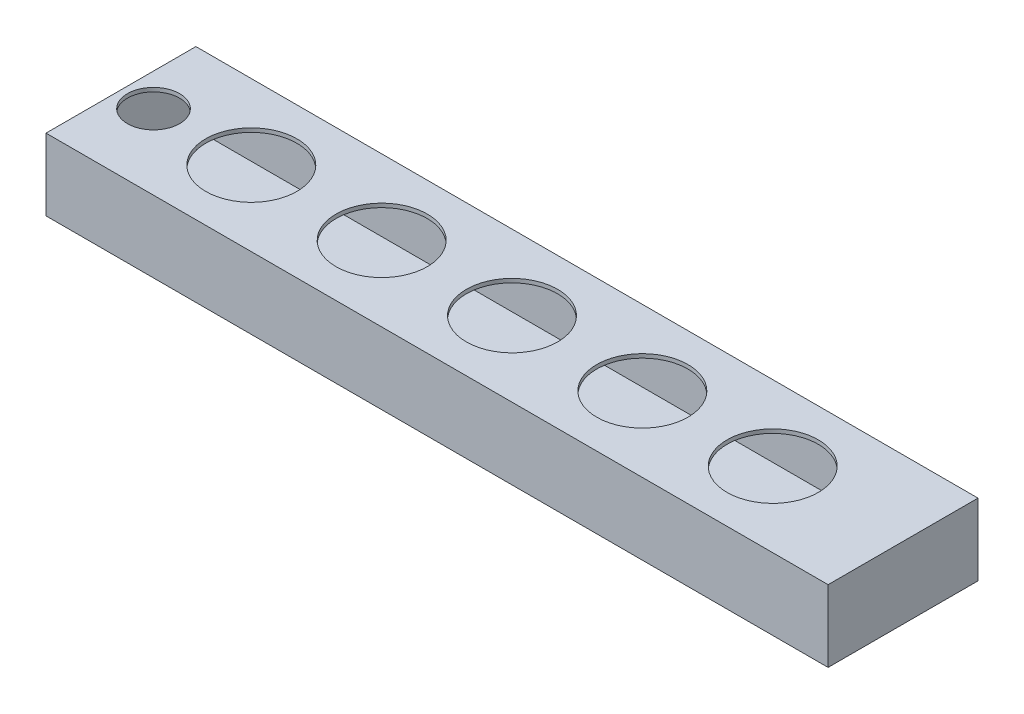
SolidWorks part; units mm, degrees
ref_plane "Спереди" through (0, 0, 0) normal (0, 0, 1) x (1, 0, 0)
ref_plane "Сверху" through (0, 0, 0) normal (0, 1, 0) x (1, 0, 0)
ref_plane "Справа" through (0, 0, 0) normal (1, 0, 0) x (0, 0, -1)
sketch "Эскиз2" plane through (0, 0, 0) normal (0, 0, 1) x (1, 0, 0)
  line L0 (0, 0) -> (600, 0)
  line L1 (600, 0) -> (600, 55)
  line L2 (600, 55) -> (0, 55)
  line L3 (0, 55) -> (0, 0)
extrude "Бобышка-Вытянуть1" add sketch "Эскиз2" along normal blind 115
sketch "Эскиз3" plane through (600, 0, 0) normal (1, 0, 0) x (0, 0, -1)
  line L3 (-112, 52) -> (-3, 52)
  line L4 (-3, 52) -> (-3, 3)
  line L5 (-3, 3) -> (-112, 3)
  line L6 (-112, 3) -> (-112, 52)
  line L7 (-115, 55) -> (-112, 52)
  line L8 (-3, 3) -> (0, 0)
  line L9 (-115, 0) -> (-115, 55) construction
  dimension "D1" = 3
  dimension "D2" = 3
extrude "Вырез-Вытянуть1" cut sketch "Эскиз3" against normal blind 600 contours L6 L5 L4 L3 region at (600, 27.5, 57.5)
sketch "Эскиз4" plane through (0, 55, 0) normal (0, 1, 0) x (1, 0, 0)
  line L0 (600, 0) -> (0, 0) construction
  line L1 (600, -115) -> (597, -115)
  line L2 (600, -115) -> (600, 0)
  line L3 (600, 0) -> (597, 0)
  line L4 (597, -115) -> (597, 0)
  line L6 (0, -115) -> (3, -115)
  line L7 (0, -115) -> (0, 0)
  line L8 (0, 0) -> (3, 0)
  line L9 (3, -115) -> (3, 0)
extrude "Бобышка-Вытянуть2" add sketch "Эскиз4" against normal blind 55
sketch "Эскиз5" plane through (0, 55, 0) normal (0, 1, 0) x (1, 0, 0)
  line L0 (0, -115) -> (5, -115)
  line L1 (600, -115) -> (0, -115) construction
  line L2 (5, -115) -> (5, -57.5)
  line L4 (0, -115) -> (0, 0) construction
  circle A0 centre (25, -57.5) radius 20
  circle A1 centre (100, -57.5) radius 35
  circle A2 centre (200, -57.5) radius 35
  circle A3 centre (300, -57.5) radius 35
  circle A4 centre (400, -57.5) radius 35
  circle A5 centre (500, -57.5) radius 35
  dimension "D3" = 40
  dimension "D5" = 70
  dimension "D1" = 5
  dimension "D2" = 57.5
  dimension "D4" = 100
  dimension "D6" = 5
extrude "Вырез-Вытянуть2" cut sketch "Эскиз5" against normal blind 3 contours A5 | A4 | A3 | A2 | A0 | A1 region at (25, 55, 57.5) region at (200, 55, 57.5) region at (300, 55, 57.5) region at (400, 55, 57.5) region at (500, 55, 57.5)
sketch "Эскиз6" plane through (0, 0, 0) normal (0, -1, 0) x (1, 0, 0)
  line L0 (0, 115) -> (600, 115) construction
  line L2 (600, 115) -> (600, 0) construction
  circle A0 centre (575, 57.5) radius 20
  dimension "D3" = 40
  dimension "D1" = 57.5
  dimension "D2" = 25
extrude "Вырез-Вытянуть3" cut sketch "Эскиз6" against normal blind 3
